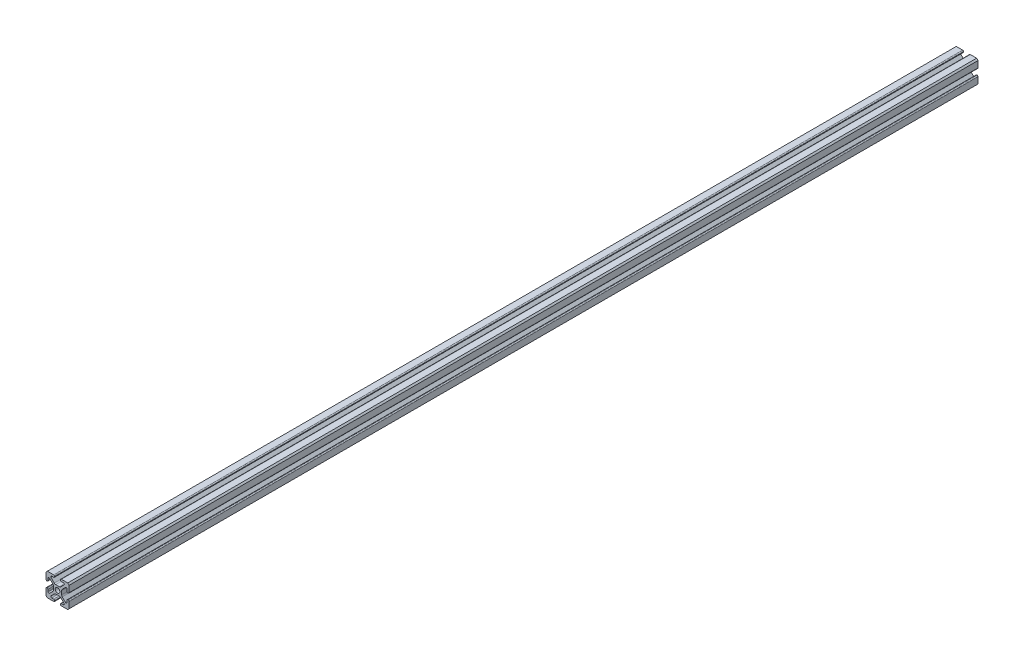
SolidWorks part; units mm, degrees
ref_plane "Front Plane" through (0, 0, 0) normal (0, 0, 1) x (1, 0, 0)
ref_plane "Top Plane" through (0, 0, 0) normal (0, 1, 0) x (1, 0, 0)
ref_plane "Right Plane" through (0, 0, 0) normal (1, 0, 0) x (0, 0, -1)
other "Configuration Table"
sketch "Sketch1" plane through (0, 0, 0) normal (0, 0, 1) x (1, 0, 0)
  line L0 (-11.2, -12.7) -> (-4.2223, -12.7)
  line L1 (-3.2063, -11.684) -> (-3.2063, -11.4407)
  line L2 (-4.2223, -10.4247) -> (-6.4093, -10.4247)
  line L3 (-7.1277, -8.6902) -> (-3.5932, -5.1557)
  line L4 (-2.0306, -4.5085) -> (2.0306, -4.5085)
  line L5 (3.5932, -5.1557) -> (7.1277, -8.6902)
  line L6 (6.4093, -10.4247) -> (4.2223, -10.4247)
  line L7 (3.2063, -11.4407) -> (3.2063, -11.684)
  line L8 (4.2223, -12.7) -> (11.2, -12.7)
  line L9 (11.2, -12.7) -> (12.7, -11.2)
  line L10 (12.7, -11.2) -> (12.7, -4.2223)
  line L11 (11.684, -3.2063) -> (11.4407, -3.2063)
  line L12 (10.4247, -4.2223) -> (10.4247, -6.4093)
  line L13 (8.6902, -7.1277) -> (5.1557, -3.5932)
  line L14 (4.5085, -2.0306) -> (4.5085, 2.0306)
  line L15 (5.1557, 3.5932) -> (8.6902, 7.1277)
  line L16 (10.4247, 6.4093) -> (10.4247, 4.2223)
  line L17 (11.4407, 3.2063) -> (11.684, 3.2063)
  line L18 (12.7, 4.2223) -> (12.7, 11.2)
  line L19 (12.7, 11.2) -> (11.2, 12.7)
  line L20 (11.2, 12.7) -> (4.2223, 12.7)
  line L21 (3.2063, 11.684) -> (3.2063, 11.4407)
  line L22 (4.2223, 10.4247) -> (6.4093, 10.4247)
  line L23 (7.1277, 8.6902) -> (3.5932, 5.1557)
  line L24 (2.0306, 4.5085) -> (-2.0306, 4.5085)
  line L25 (-3.5932, 5.1557) -> (-7.1277, 8.6902)
  line L26 (-6.4093, 10.4247) -> (-4.2223, 10.4247)
  line L27 (-3.2063, 11.4407) -> (-3.2063, 11.684)
  line L28 (-4.2223, 12.7) -> (-11.2, 12.7)
  line L29 (-11.2, 12.7) -> (-12.7, 11.2)
  line L30 (-12.7, 11.2) -> (-12.7, 4.2223)
  line L31 (-11.684, 3.2063) -> (-11.4407, 3.2063)
  line L32 (-10.4247, 4.2223) -> (-10.4247, 6.4093)
  line L33 (-8.6902, 7.1277) -> (-5.1557, 3.5932)
  line L34 (-4.5085, 2.0306) -> (-4.5085, -2.0306)
  line L35 (-5.1557, -3.5932) -> (-8.6902, -7.1277)
  line L36 (-10.4247, -6.4093) -> (-10.4247, -4.2223)
  line L37 (-11.4407, -3.2063) -> (-11.684, -3.2063)
  line L38 (-12.7, -4.2223) -> (-12.7, -11.2)
  line L39 (-12.7, -11.2) -> (-11.2, -12.7)
  arc A0 (-2.555, 0) -> (2.555, 0) centre (0, 0) ccw
  arc A1 (2.555, 0) -> (-2.555, 0) centre (0, 0) ccw
  arc A2 (-4.2223, -12.7) -> (-3.2063, -11.684) centre (-4.2223, -11.684) ccw
  arc A3 (-3.2063, -11.4407) -> (-4.2223, -10.4247) centre (-4.2223, -11.4407) ccw
  arc A4 (-7.1277, -8.6902) -> (-6.4093, -10.4247) centre (-6.4093, -9.4087) ccw
  arc A5 (-2.0306, -4.5085) -> (-3.5932, -5.1557) centre (-2.0306, -6.7183) ccw
  arc A6 (3.5932, -5.1557) -> (2.0306, -4.5085) centre (2.0306, -6.7183) ccw
  arc A7 (7.4253, -9.4087) -> (7.1277, -8.6902) centre (6.4093, -9.4087) ccw
  arc A8 (6.4093, -10.4247) -> (7.4253, -9.4087) centre (6.4093, -9.4087) ccw
  arc A9 (4.2223, -10.4247) -> (3.2063, -11.4407) centre (4.2223, -11.4407) ccw
  arc A10 (3.2063, -11.684) -> (4.2223, -12.7) centre (4.2223, -11.684) ccw
  arc A11 (12.7, -4.2223) -> (11.684, -3.2063) centre (11.684, -4.2223) ccw
  arc A12 (11.4407, -3.2063) -> (10.4247, -4.2223) centre (11.4407, -4.2223) ccw
  arc A13 (8.6902, -7.1277) -> (10.4247, -6.4093) centre (9.4087, -6.4093) ccw
  arc A14 (4.5085, -2.0306) -> (5.1557, -3.5932) centre (6.7183, -2.0306) ccw
  arc A15 (5.1557, 3.5932) -> (4.5085, 2.0306) centre (6.7183, 2.0306) ccw
  arc A16 (9.4087, 7.4253) -> (8.6902, 7.1277) centre (9.4087, 6.4093) ccw
  arc A17 (10.4247, 6.4093) -> (9.4087, 7.4253) centre (9.4087, 6.4093) ccw
  arc A18 (10.4247, 4.2223) -> (11.4407, 3.2063) centre (11.4407, 4.2223) ccw
  arc A19 (11.684, 3.2063) -> (12.7, 4.2223) centre (11.684, 4.2223) ccw
  arc A20 (4.2223, 12.7) -> (3.2063, 11.684) centre (4.2223, 11.684) ccw
  arc A21 (3.2063, 11.4407) -> (4.2223, 10.4247) centre (4.2223, 11.4407) ccw
  arc A22 (7.1277, 8.6902) -> (6.4093, 10.4247) centre (6.4093, 9.4087) ccw
  arc A23 (2.0306, 4.5085) -> (3.5932, 5.1557) centre (2.0306, 6.7183) ccw
  arc A24 (-3.5932, 5.1557) -> (-2.0306, 4.5085) centre (-2.0306, 6.7183) ccw
  arc A25 (-7.4253, 9.4087) -> (-7.1277, 8.6902) centre (-6.4093, 9.4087) ccw
  arc A26 (-6.4093, 10.4247) -> (-7.4253, 9.4087) centre (-6.4093, 9.4087) ccw
  arc A27 (-4.2223, 10.4247) -> (-3.2063, 11.4407) centre (-4.2223, 11.4407) ccw
  arc A28 (-3.2063, 11.684) -> (-4.2223, 12.7) centre (-4.2223, 11.684) ccw
  arc A29 (-12.7, 4.2223) -> (-11.684, 3.2063) centre (-11.684, 4.2223) ccw
  arc A30 (-11.4407, 3.2063) -> (-10.4247, 4.2223) centre (-11.4407, 4.2223) ccw
  arc A31 (-8.6902, 7.1277) -> (-10.4247, 6.4093) centre (-9.4087, 6.4093) ccw
  arc A32 (-4.5085, 2.0306) -> (-5.1557, 3.5932) centre (-6.7183, 2.0306) ccw
  arc A33 (-5.1557, -3.5932) -> (-4.5085, -2.0306) centre (-6.7183, -2.0306) ccw
  arc A34 (-9.4087, -7.4253) -> (-8.6902, -7.1277) centre (-9.4087, -6.4093) ccw
  arc A35 (-10.4247, -6.4093) -> (-9.4087, -7.4253) centre (-9.4087, -6.4093) ccw
  arc A36 (-10.4247, -4.2223) -> (-11.4407, -3.2063) centre (-11.4407, -4.2223) ccw
  arc A37 (-11.684, -3.2063) -> (-12.7, -4.2223) centre (-11.684, -4.2223) ccw
extrude "Boss-Extrude1" add sketch "Sketch1" along normal blind 1000.21
equation "\"Extrusion Length\"= 24"
